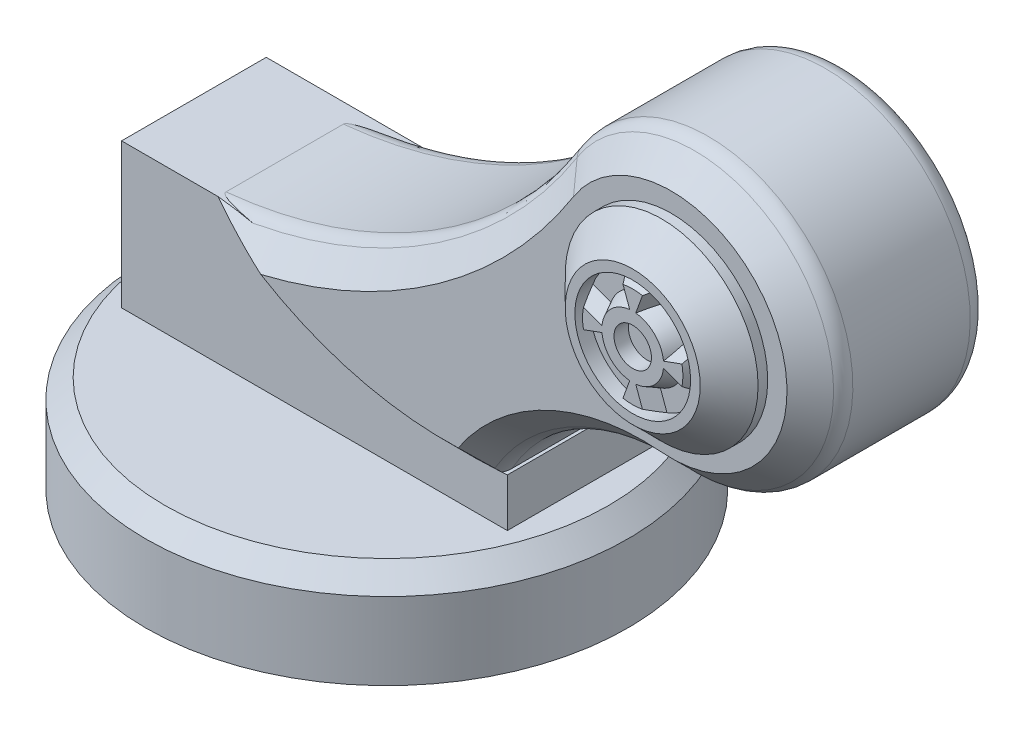
SolidWorks part; units mm, degrees
ref_plane "Front Plane" through (0, 0, 0) normal (0, 0, 1) x (1, 0, 0)
ref_plane "Top Plane" through (0, 0, 0) normal (0, 1, 0) x (1, 0, 0)
ref_plane "Right Plane" through (0, 0, 0) normal (1, 0, 0) x (0, 0, -1)
sketch "Sketch1" plane through (0, 0, 0) normal (0, 1, 0) x (1, 0, 0)
  circle A0 centre (0, 0) radius 31.75
  dimension "D1" = 63.5
extrude "Boss-Extrude1" add sketch "Sketch1" along normal blind 12.7
chamfer "Chamfer2" distance 2.54 angle 45 1 edges at (0, 12.7, 31.75)
sketch "Sketch3" plane through (0, 12.7, 0) normal (0, 1, 0) x (1, 0, 0)
  line L1 (25.4, -9.525) -> (-25.4, -9.525)
  line L2 (25.4, -9.525) -> (25.4, 9.525)
  line L3 (25.4, 9.525) -> (-25.4, 9.525)
  line L4 (-25.4, -9.525) -> (-25.4, 9.525)
  line L5 (25.4, -9.525) -> (-25.4, 9.525) construction
  line L6 (25.4, 9.525) -> (-25.4, -9.525) construction
  point P0 (0, 0)
  dimension "D1" = 50.8
  dimension "D2" = 19.05
extrude "Boss-Extrude3" add sketch "Sketch3" along normal blind 19.05
sketch "Sketch4" plane through (0, 0, -9.525) normal (0, 0, -1) x (-1, 0, 0)
  line L0 (-25.4, 31.75) -> (12.7, 31.75)
  line L1 (-25.4, 31.75) -> (25.4, 31.75) construction
  line L2 (-25.4, 31.75) -> (-25.4, 19.05)
  line L3 (-25.4, 31.75) -> (-25.4, 12.7) construction
  arc A0 (12.7, 31.75) -> (-25.4, 19.05) centre (-21.1061, 69.6682) cw
  dimension "D1" = 38.1
  dimension "D2" = 12.7
extrude "Cut-Extrude1" cut sketch "Sketch4" against normal blind 19.05
sketch "Sketch6" plane through (0, 0, 0) normal (0, 0, 1) x (1, 0, 0)
  line L0 (0, 0) -> (50.8, 0)
  line L1 (50.8, 0) -> (50.8, 50.8)
  circle A0 centre (50.8, 50.8) radius 19.05
  arc A1 (49.1893, 31.8182) -> (24.9323, 19.0125) centre (47.0417, 6.5092) ccw
  arc A2 (-12.7, 31.75) -> (25.4, 19.05) centre (21.1061, 69.6682) ccw construction
  arc A3 (34.7022, 60.9864) -> (-12.7, 31.75) centre (-18.9573, 94.941) cw
  arc A4 (-12.7, 31.75) -> (24.9323, 19.0125) centre (21.1061, 69.6682) ccw
  dimension "D3" = 38.1
  dimension "D4" = 63.5
  dimension "D5" = 25.4
  dimension "D1" = 50.8
  dimension "D2" = 50.8
extrude "Boss-Extrude5" add sketch "Sketch6" against normal mid plane 19.05 contours A3 A4 A1 A0 | A0 region at (63.8894, 37.7106, 0) region at (18.5255, 32.8044, 0)
sketch "Sketch9" plane through (0, 0, 9.525) normal (0, 0, 1) x (1, 0, 0)
  arc A0 (49.1893, 31.8182) -> (24.9323, 19.0125) centre (47.0417, 6.5092) ccw construction
  circle A1 centre (50.8, 50.8) radius 19.05 construction
  arc A2 (-12.7, 31.75) -> (34.7022, 60.9864) centre (-18.9573, 94.941) ccw construction
  arc A3 (-12.7, 31.75) -> (24.9323, 19.0125) centre (21.1061, 69.6682) ccw construction
  arc A4 (49.1893, 31.8182) -> (24.9323, 19.0125) centre (47.0417, 6.5092) ccw
  circle A5 centre (50.8, 50.8) radius 19.05
  arc A6 (-12.7, 31.75) -> (34.7022, 60.9864) centre (-18.9573, 94.941) ccw
  arc A7 (-12.7, 31.75) -> (24.9323, 19.0125) centre (21.1061, 69.6682) ccw
  arc M3 (24.9323, 19.0125) -> (49.1893, 31.8182) centre (47.0417, 6.5092) cw
  arc M4 (49.1893, 31.8182) -> (34.7022, 60.9864) centre (50.8, 50.8) ccw
  arc M5 (34.7022, 60.9864) -> (-12.7, 31.75) centre (-18.9573, 94.941) cw
extrude "Boss-Extrude6" add sketch "Sketch9" along normal blind 3.81 draft 45 contours A7 A5 M5 M3 | A5 M4 region at (18.5255, 32.8044, 9.525) region at (50.8, 50.8, 9.525)
sketch "Sketch10" plane through (0, 0, 13.335) normal (0, 0, 1) x (1, 0, 0)
  circle A0 centre (50.8, 50.8) radius 12.7
  arc A1 (49.5114, 35.6146) -> (37.9217, 58.9491) centre (50.8, 50.8) ccw construction
  dimension "0.1" = 25.4
extrude "Boss-Extrude7" add sketch "Sketch10" along normal blind 1.27
sketch "Sketch11" plane through (0, 0, 14.605) normal (0, 0, 1) x (1, 0, 0)
  circle A1 centre (50.8, 50.8) radius 12.7
  circle A2 centre (50.8, 50.8) radius 12.7
  dimension "D1" = 0
extrude "Boss-Extrude8" add sketch "Sketch11" along normal blind 3.81 draft 45
sketch "Sketch12" plane through (0, 0, 18.415) normal (0, 0, 1) x (1, 0, 0)
  circle A0 centre (50.8, 50.8) radius 7.62
  circle A1 centre (50.8, 50.8) radius 8.89 construction
  dimension "0.5" = 15.24
extrude "Cut-Extrude2" cut sketch "Sketch12" against normal blind 1.905
sketch "Sketch13" plane through (0, 0, 16.51) normal (0, 0, 1) x (1, 0, 0)
  line L0 (49.0611, 55.5775) -> (48.1938, 57.9605)
  line L1 (55.5775, 52.5389) -> (57.9605, 53.4062)
  line L2 (52.5389, 55.5775) -> (53.4062, 57.9605)
  line L3 (55.5775, 49.0611) -> (57.9605, 48.1938)
  line L4 (52.5389, 46.0225) -> (53.4062, 43.6395)
  line L5 (49.0611, 46.0225) -> (48.1938, 43.6395)
  line L6 (46.0225, 49.0611) -> (43.6395, 48.1938)
  line L7 (46.0225, 52.5389) -> (43.6395, 53.4062)
  arc A0 (49.0611, 55.5775) -> (46.0225, 52.5389) centre (50.8, 50.8) ccw
  circle A1 centre (50.8, 50.8) radius 7.62 construction
  arc A2 (46.0225, 49.0611) -> (49.0611, 46.0225) centre (50.8, 50.8) ccw
  arc A3 (52.5389, 46.0225) -> (55.5775, 49.0611) centre (50.8, 50.8) ccw
  arc A4 (55.5775, 52.5389) -> (52.5389, 55.5775) centre (50.8, 50.8) ccw
  circle A5 centre (50.8, 50.8) radius 7.62
  point P24 (50.8, 50.8)
  circle M4 centre (50.8, 50.8) radius 7.62
  dimension "D1" = 4
extrude "Boss-Extrude10" add sketch "Sketch13" along normal blind 1.905 draft 28 contours L1 A4 L2 L0 A0 L7 L6 A2 L5 L4 A3 L3 M4 region at (50.8, 50.8, 16.51)
sketch "Sketch14" plane through (0, 0, 18.415) normal (0, 0, 1) x (1, 0, 0)
  circle A0 centre (50.8, 50.8) radius 2.4665
  circle A1 centre (50.8, 50.8) radius 7.62 construction
extrude "Cut-Extrude3" cut sketch "Sketch14" against normal blind 1.905
fillet "Fillet2" radius 2.54 3 edges at (35.1836, 28.9712, 9.525) (67.8615, 59.274, 9.525) (14.3773, 40.8942, 9.525)
fillet "Fillet5" radius 2.54 3 edges at (35.1836, 28.9712, -9.525) (14.3773, 40.8942, -9.525) (67.8615, 59.274, -9.525)
sketch "Sketch15" plane through (0, 0, -9.525) normal (0, 0, -1) x (-1, 0, 0)
  circle A0 centre (-50.8, 50.8) radius 6.35
  arc A1 (-36.8485, 59.6282) -> (-49.4041, 34.3491) centre (-50.8, 50.8) ccw construction
  dimension "D1" = 12.7
extrude "Cut-Extrude4" cut sketch "Sketch15" against normal blind 2.54
sketch "Sketch16" plane through (0, 0, 0) normal (0, -1, 0) x (1, 0, 0)
  circle A0 centre (0, 0) radius 6.35
  dimension "D1" = 12.7
extrude "Cut-Extrude5" cut sketch "Sketch16" against normal blind 6.35
